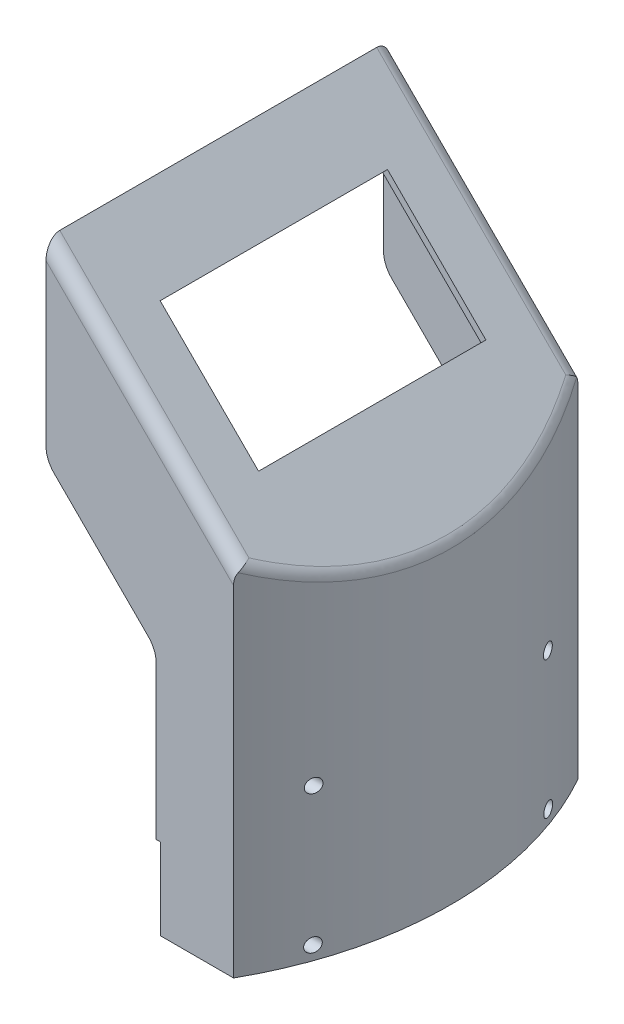
SolidWorks part; units mm, degrees
ref_plane "Front Plane" through (0, 0, 0) normal (0, 0, 1) x (1, 0, 0)
ref_plane "Top Plane" through (0, 0, 0) normal (0, 1, 0) x (1, 0, 0)
ref_plane "Right Plane" through (0, 0, 0) normal (1, 0, 0) x (0, 0, -1)
sketch "Sketch1" plane through (0, 0, 0) normal (0, 1, 0) x (1, 0, 0)
  circle A0 centre (0, 0) radius 254.5
  circle A1 centre (0, 0) radius 234.5
  dimension "D1" = 20
extrude "Boss-Extrude1" add sketch "Sketch1" along normal blind 5
sketch "Sketch2" plane through (0, 5, 0) normal (0, 1, 0) x (1, 0, 0)
  line L0 (254.5, 0) -> (234.5, 0)
  line L1 (221.6873, 125) -> (198.4068, 125)
  line L3 (168.5, 125) -> (165.5, 125) construction
  arc A0 (254.5, 0) -> (221.6873, 125) centre (0, 0) ccw
  circle A2 centre (0, 0) radius 254.5 construction
  circle A7 centre (0, 0) radius 234.5 construction
  arc A8 (198.4068, 125) -> (234.5, 0) centre (0, 0) cw
  circle M1 centre (0, 0) radius 254.5
  circle M2 centre (0, 0) radius 234.5
  dimension "D1" = 0
  dimension "D2" = 0
extrude "Boss-Extrude2" add sketch "Sketch2" along normal blind 500 contours L1 M1 M2 region at (232.9072, 5, -64.0481)
mirror "Mirror1" about plane through (0, 505, 0) normal (0, 0, 1) of "Boss-Extrude2"
sketch "Sketch3" plane through (0, 5, 0) normal (0, 1, 0) x (1, 0, 0)
  line L1 (-254.5, 0) -> (-226.6942, 0)
  line L2 (-254.5, 0) -> (-254.5, 60)
  line L3 (-254.5, 60) -> (-226.6942, 60)
  line L4 (-226.6942, 0) -> (-226.6942, 60)
  arc A0 (221.6873, 125) -> (221.6873, -125) centre (0, 0) ccw construction
  arc A1 (198.4068, 125) -> (198.4068, -125) centre (0, 0) ccw construction
  dimension "D1" = 60
extrude "Cut-Extrude1" cut sketch "Sketch3" against normal blind 500
mirror "Mirror2" about plane through (0, 0, 0) normal (0, 0, 1) of "Cut-Extrude1"
sketch "Sketch4" plane through (0, 505, 0) normal (0, 1, 0) x (1, 0, 0)
  circle A0 centre (0, 0) radius 250.5
  arc A1 (221.6873, -125) -> (221.6873, 125) centre (0, 0) ccw construction
  dimension "D1" = 4
extrude "Cut-Extrude2" cut sketch "Sketch4" against normal blind 500
sketch "Sketch8" plane through (0, 5, 0) normal (0, 1, 0) x (1, 0, 0)
  line L0 (217.0835, 125) -> (165.5835, 125)
  line L1 (165.5835, 125) -> (165.5835, 120)
  line L2 (165.5835, 120) -> (220.0458, 120)
  line L3 (220.0458, 120) -> (220.0458, 125)
  line L4 (221.6873, 125) -> (217.0835, 125) construction
  line L5 (220.0458, 125) -> (217.0835, 125)
  dimension "D1" = 5
  dimension "D2" = 51.5
  dimension "D3" = 220.0458
extrude "Boss-Extrude3" add sketch "Sketch8" along normal blind 500
mirror "Mirror3" about plane through (0, 0, 0) normal (0, 0, 1) of "Boss-Extrude3"
sketch "Sketch10" plane through (0, 0, 0) normal (0, -1, 0) x (1, 0, 0)
  line L0 (165.5835, 125) -> (165.5835, -125)
  line L1 (165.5835, 125) -> (208.5835, 125)
  line L2 (165.5835, -125) -> (208.5835, -125)
  arc A3 (208.5835, 125) -> (208.5835, -125) centre (0, 0) cw
  arc M3 (-226.6942, 60) -> (-226.6942, -60) centre (0, 0) cw
extrude "Boss-Extrude4" add sketch "Sketch10" against normal blind 5 contours L0 L2 L1 M3 region at (195.2098, 0, 0)
sketch "Sketch11" plane through (0, 5, 0) normal (0, 1, 0) x (1, 0, 0)
  line L0 (165.5835, -120) -> (165.5835, 120) construction
  line L1 (165.5835, 93.5) -> (190, 93.5)
  line L2 (165.5835, 93.5) -> (165.5835, -96.5)
  line L3 (165.5835, -96.5) -> (190, -96.5)
  line L4 (190, 93.5) -> (190, -96.5)
  line L5 (188.5, -95) -> (188.5, -75) construction
  line L6 (168.5, -95) -> (188.5, -95) construction
  line L7 (188.5, 95) -> (168.5, 95) construction
  point P10 (178.5, -95)
  dimension "D1" = 1.5
  dimension "D2" = 1.5
  dimension "D3" = 1.5
extrude "Cut-Extrude3" cut sketch "Sketch11" against normal blind 10
sketch "Sketch12" plane through (0, 5, 0) normal (0, 1, 0) x (1, 0, 0)
  line L0 (-276.0044, 0) -> (276.0044, 0) construction
  line L1 (165.5835, 120) -> (185, 120)
  line L2 (165.5835, 120) -> (165.5835, 93.5)
  line L3 (165.5835, 93.5) -> (190, 93.5)
  line L4 (190, 115) -> (190, 93.5)
  line L5 (190, 93.5) -> (213, 93.5)
  line L6 (190, 93.5) -> (190, 75)
  line L7 (190, 75) -> (213, 75)
  line L8 (218, 88.5) -> (218, 80)
  line L9 (218, -88.5) -> (218, -80)
  line L10 (190, -75) -> (213, -75)
  line L11 (190, -93.5) -> (190, -75)
  line L12 (190, -93.5) -> (213, -93.5)
  line L13 (190, -115) -> (190, -93.5)
  line L14 (165.5835, -93.5) -> (190, -93.5)
  line L15 (165.5835, -120) -> (165.5835, -93.5)
  line L16 (165.5835, -120) -> (185, -120)
  arc A0 (213, -93.5) -> (218, -88.5) centre (213, -88.5) ccw
  arc A1 (218, -80) -> (213, -75) centre (213, -80) ccw
  arc A2 (190, -115) -> (185, -120) centre (185, -115) cw
  arc A3 (213, 75) -> (218, 80) centre (213, 80) ccw
  arc A4 (218, 88.5) -> (213, 93.5) centre (213, 88.5) ccw
  arc A5 (190, 115) -> (185, 120) centre (185, 115) ccw
  point P20 (218, -93.5)
  point P23 (218, -75)
  point P26 (190, -120)
  point P29 (218, 75)
  point P32 (218, 93.5)
  point P35 (190, 120)
  line M3 (190, 93.5) -> (190, -96.5)
  line M4 (190, -96.5) -> (165.5835, -96.5)
  line M5 (165.5835, -96.5) -> (165.5835, -120)
  line M6 (165.5835, -120) -> (219.8869, -120)
  dimension "D2" = 5
  dimension "D1" = 28
extrude "Cut-Extrude4" cut sketch "Sketch12" against normal blind 10 contours L8 L5 L7 M3 | L9 A1 L10 L12 A0 M3 | A2 L13 M4 M5 M6 | L4 A5 L1 L2 L3 region at (203.7275, 5, 84.25) region at (203.7275, 5, -84.25) region at (177.6871, 5, 108.1496)
fillet "Fillet1" radius 5 4 edges at (190, 2.5, 93.5) (190, 2.5, -93.5) (190, 2.5, -75) (190, 2.5, 75)
sketch "Sketch15" plane through (0, 5, 0) normal (0, 1, 0) x (1, 0, 0)
  circle A0 centre (242.5, 0) radius 2.5
  circle A1 centre (196.1866, -142.5379) radius 2.5
  circle A2 centre (74.9366, -230.6312) radius 2.5
  circle A3 centre (-74.9366, -230.6312) radius 2.5
  circle A4 centre (-196.1866, -142.5379) radius 2.5
  circle A5 centre (-242.5, 0) radius 2.5
  circle A6 centre (-196.1866, 142.5379) radius 2.5
  circle A7 centre (-74.9366, 230.6312) radius 2.5
  circle A8 centre (74.9366, 230.6312) radius 2.5
  circle A9 centre (196.1866, 142.5379) radius 2.5
  point P23 (0, 0)
  dimension "D1" = 242.5
  dimension "D2" = 10
extrude "Cut-Extrude5" cut sketch "Sketch15" against normal blind 10
sketch "Sketch16" plane through (0, 5, 0) normal (0, 1, 0) x (1, 0, 0)
  line L0 (-226.6942, 60) -> (-247.3262, 60) construction
  line L1 (221.6873, 125) -> (198.4068, 125) construction
  line L2 (-247.3262, 60) -> (-244.2381, 60)
  line L3 (221.6873, 125) -> (218.2367, 125)
  line L4 (-276.0044, 0) -> (276.0044, 0) construction
  line L5 (221.6873, -125) -> (218.2367, -125)
  line L6 (-247.3262, -60) -> (-244.2381, -60)
  arc A0 (221.6873, 125) -> (-247.3262, 60) centre (0, 0) ccw
  arc A1 (218.2367, 125) -> (-244.2381, 60) centre (0, 0) ccw
  arc A2 (218.2367, -125) -> (-244.2381, -60) centre (0, 0) cw
  arc A3 (221.6873, -125) -> (-247.3262, -60) centre (0, 0) cw
  dimension "D1" = 3
extrude "Boss-Extrude5" add sketch "Sketch16" along normal blind 3
sketch "Sketch18" plane through (0, 5, 0) normal (0, 1, 0) x (1, 0, 0)
  circle A0 centre (0, -242.5) radius 2.5
  circle A1 centre (-142.5379, -196.1866) radius 2.5
  circle A2 centre (-230.6312, -74.9366) radius 2.5
  circle A3 centre (-230.6312, 74.9366) radius 2.5
  circle A4 centre (-142.5379, 196.1866) radius 2.5
  circle A5 centre (0, 242.5) radius 2.5
  circle A6 centre (142.5379, 196.1866) radius 2.5
  circle A7 centre (230.6312, 74.9366) radius 2.5
  circle A8 centre (230.6312, -74.9366) radius 2.5
  circle A9 centre (142.5379, -196.1866) radius 2.5
  point P23 (0, 0)
  dimension "D1" = 242.5
  dimension "D2" = 10
extrude "Cut-Extrude6" cut sketch "Sketch18" against normal blind 5
sketch "Sketch19" plane through (0, 0, 0) normal (0, -1, 0) x (1, 0, 0)
  line L1 (193, 20) -> (207, 20)
  line L2 (190, 17) -> (190, -17)
  line L3 (193, -20) -> (207, -20)
  line L4 (210, 17) -> (210, -17)
  line L5 (193, -20) -> (190, -20)
  line L7 (190, -20) -> (190, -17)
  line L8 (193, 20) -> (190, 20)
  line L9 (190, 20) -> (190, 17)
  arc A1 (207, -20) -> (210, -17) centre (207, -17) ccw
  arc A2 (210, 17) -> (207, 20) centre (207, 17) ccw
  point P14 (190, 20)
extrude "Cut-Extrude7" cut sketch "Sketch19" against normal blind 7
fillet "Fillet2" radius 5 2 edges at (190, 2.5, 20) (190, 2.5, -20)
sketch "Sketch21" plane through (0, 5, 0) normal (0, 1, 0) x (1, 0, 0)
  line L0 (207, 20) -> (195, 20) construction
  line L1 (195, -20) -> (207, -20) construction
  line L2 (190, 25) -> (190, 70) construction
  line L3 (190, -70) -> (190, -25) construction
  circle A0 centre (200, 50) radius 2.5
  circle A1 centre (200, -50) radius 2.5
  dimension "D1" = 30
  dimension "D2" = 30
  dimension "D3" = 10
  dimension "D4" = 10
extrude "Cut-Extrude8" cut sketch "Sketch21" against normal blind 10
sketch "Sketch24" plane through (0, 0, 0) normal (0, 0, 1) x (1, 0, 0)
  line L0 (254.5, 0) -> (254.5, 505) construction
  line L1 (268.5989, 234) -> (240.4011, 234)
  line L2 (268.5989, 234) -> (268.5989, 259)
  line L3 (268.5989, 259) -> (240.4011, 259)
  line L4 (240.4011, 234) -> (240.4011, 259)
  line L5 (268.5989, 234) -> (240.4011, 259) construction
  line L6 (268.5989, 259) -> (240.4011, 234) construction
  line L7 (221.6873, 8) -> (-247.3262, 8) construction
  point P0 (254.5, 246.5)
  dimension "D1" = 226
  dimension "D2" = 25
extrude "Cut-Extrude11" cut sketch "Sketch24" against normal mid plane 90
fillet "Fillet3" radius 2 4 edges at (248.4575, 259, 45) (248.4575, 234, 45) (248.4575, 234, -45) (248.4575, 259, -45)
sketch "Sketch25" plane through (0, 0, 0) normal (0, -1, 0) x (1, 0, 0)
  circle A0 centre (0, 0) radius 315.9931
extrude "Cut-Extrude12" cut sketch "Sketch25" against normal blind 277
sketch "Sketch26" plane through (0, 277, 0) normal (0, -1, 0) x (1, 0, 0)
  line L0 (188.5835, -120) -> (188.5835, -60)
  line L1 (165.5835, -120) -> (219.8869, -120) construction
  line L2 (165.5835, 120) -> (219.8869, 120) construction
  line L4 (188.5835, -120) -> (219.8869, -120)
  line L5 (188.5835, 120) -> (219.8869, 120)
  line L6 (188.5835, -60) -> (243.2082, -60)
  line L7 (188.5835, 120) -> (188.5835, 60)
  line L8 (188.5835, 60) -> (243.2082, 60)
  arc A0 (219.8869, -120) -> (250.5, 0) centre (0, 0) cw
  arc A1 (219.8869, -120) -> (219.8869, 120) centre (0, 0) ccw construction
  line M9 (165.5835, 120) -> (219.8869, 120)
  arc M10 (219.8869, 120) -> (219.8869, -120) centre (0, 0) cw
  line M11 (219.8869, -120) -> (165.5835, -120)
  dimension "D1" = 60
  dimension "D2" = 54.6247
extrude "Boss-Extrude6" add sketch "Sketch26" against normal blind 150 contours L6 L0 M11 M10 | L7 L8 M10 M9 region at (211.3196, 277, -87.3868) region at (211.3196, 277, 87.3868)
sketch "Sketch30" plane through (0, 505, 0) normal (0, 1, 0) x (1, 0, 0)
  line L12 (219.8869, 120) -> (217.6057, 120)
  line L13 (219.8869, 120) -> (188.5835, 120) construction
  line L14 (219.8869, -120) -> (217.6057, -120)
  line L15 (188.5835, -120) -> (219.8869, -120) construction
  arc A4 (218.1313, -119.0419) -> (218.1313, 119.0419) centre (0, 0) ccw
  arc A5 (218.1313, -119.0419) -> (218.1313, 119.0419) centre (0, 0) ccw
  circle A6 centre (0, 0) radius 248.5
  arc A7 (219.8869, -120) -> (219.8869, 120) centre (0, 0) ccw
  arc A8 (219.8869, -120) -> (219.8869, 120) centre (0, 0) ccw
  line M8 (165.5835, 120) -> (219.8869, 120)
  arc M9 (219.8869, 120) -> (219.8869, -120) centre (0, 0) cw
  line M10 (219.8869, -120) -> (165.5835, -120)
  dimension "D1" = 2
  dimension "D2" = 0
extrude "Boss-Extrude8" add sketch "Sketch30" against normal blind 228 contours A6 A5 M10 M9 M8 region at (250.2578, 505, 0)
sketch "Sketch33" plane through (0, 0, 0) normal (0, 0, 1) x (1, 0, 0)
  line L0 (254.5, 505) -> (85.5835, 673.9165)
  line L2 (165.5835, 505) -> (254.5, 505)
  line L3 (165.5835, 505) -> (85.5835, 505)
  line L6 (85.5835, 505) -> (85.5835, 673.9165)
  point P3 (88.5835, 670.7629)
  point P7 (88.5835, 672.6248)
  dimension "D1" = 45
  dimension "D2" = 80
extrude "Boss-Extrude9" add sketch "Sketch33" along normal mid plane 250
sketch "Sketch34" plane through (0, 505, 0) normal (0, -1, 0) x (-1, 0, 0)
  line L0 (-221.6873, -125) -> (-254.5, -125)
  line L1 (-254.5, -125) -> (-254.5, 0) construction
  line L2 (-254.5, -125) -> (-254.5, 126.7594)
  line L3 (-221.6873, 125) -> (-254.5, 125)
  arc A0 (-221.6873, -125) -> (-254.5, 0) centre (0, 0) ccw
  arc A1 (-221.6873, 125) -> (-221.6873, -125) centre (0, 0) ccw construction
  line M1 (-254.5, -125) -> (-221.6873, -125)
  arc M2 (-221.6873, -125) -> (-254.5, 0) centre (0, 0) cw
  line M3 (-254.5, 0) -> (-254.5, -125)
extrude "Cut-Extrude15" cut sketch "Sketch34" against normal blind 250 contours M3 M1 M2 | A0 L3 L2 region at (244.7754, 505, 94.1672) region at (244.7754, 505, -94.1672)
sketch "Sketch35" plane through (188.5835, 0, 0) normal (-1, 0, 0) x (0, 0, 1)
  line L0 (-120, 277) -> (-60, 277) construction
  line L1 (-120, 427) -> (-120, 277) construction
  line L2 (0, -48.9041) -> (0, 48.9041) construction
  circle A0 centre (-85, 386.9994) radius 2.5
  circle A1 centre (-85.3604, 287) radius 2.5
  circle A2 centre (85.3604, 287) radius 2.5
  circle A3 centre (85, 386.9994) radius 2.5
  dimension "D1" = 100
  dimension "D2" = 10
  dimension "D3" = 35
extrude "Cut-Extrude16" cut sketch "Sketch35" against normal blind 10
sketch "Sketch37" plane through (0, 0, 0) normal (0, 0, 1) x (1, 0, 0)
  line L0 (85.5835, 666.8454) -> (85.5835, 505)
  line L1 (85.5835, 505) -> (165.5835, 505) construction
  line L2 (85.5835, 505) -> (217.6057, 505)
  line L3 (217.6057, 534.8232) -> (85.5835, 666.8454)
  line L7 (221.6873, 537.8127) -> (85.5835, 673.9165) construction
  line L8 (217.6057, 427) -> (217.6057, 505) construction
  line L10 (217.6057, 505) -> (217.6057, 534.8232)
  line L11 (85.5835, 673.9165) -> (85.5835, 505) construction
  point P5 (217.6057, 534.8654)
  point P13 (217.4488, 534.9801)
  dimension "D1" = 0
  dimension "D2" = 5
extrude "Cut-Extrude18" cut sketch "Sketch37" against normal mid plane 240 contours L2 L3 L0 region at (136.4384, 560.4953, 0)
sketch "Sketch40" plane through (0, 0, -125) normal (0, 0, -1) x (-1, 0, 0)
  line L0 (-165.5835, 505) -> (-85.5835, 585)
  line L2 (-85.5835, 585) -> (-85.5835, 505)
  line L3 (-85.5835, 505) -> (-165.5835, 505)
  line L4 (-85.5835, 673.9165) -> (-85.5835, 505) construction
  line L5 (-221.6873, 537.8127) -> (-85.5835, 673.9165) construction
  dimension "D1" = 0
  dimension "D2" = 0
extrude "Cut-Extrude19" cut sketch "Sketch40" against normal blind 369
sketch "Sketch41" plane through (0, 505, 0) normal (0, -1, 0) x (1, 0, 0)
  line L0 (217.6057, 120) -> (217.6057, -120)
  circle A0 centre (0, 0) radius 248.5
  arc M1 (217.6057, -120) -> (217.6057, 120) centre (0, 0) ccw
  line M2 (217.6057, 120) -> (217.6057, -120)
extrude "Boss-Extrude10" add sketch "Sketch41" along normal blind 228 contours M2 M1 region at (230.0317, 505, 0)
sketch "Sketch36" plane through (198.5835, 0, 0) normal (-1, 0, 0) x (0, 0, 1)
  line L0 (0, -48.9041) -> (0, 48.9041) construction
  circle A0 centre (-85, 386.9994) radius 5
  circle A1 centre (-85.3604, 287) radius 5
  circle A2 centre (85.3604, 287) radius 5
  circle A3 centre (85, 386.9994) radius 5
extrude "Cut-Extrude17" cut sketch "Sketch36" against normal blind 110
fillet "Fillet5" radius 10 1 edges at (217.6057, 534.8232, 0)
fillet "Fillet7" radius 10 3 edges at (153.6354, 605.8646, 125) (254.5, 505, 0) (153.6354, 605.8646, -125)
sketch "Sketch43" plane through (376.2145, 376.2145, 0) normal (-0.7071, -0.7071, 0) x (0, 0, 1)
  line L0 (-120, 228.4488) -> (120, 228.4488) construction
  line L1 (82.5, 257.9488) -> (-82.5, 257.9488)
  line L2 (82.5, 257.9488) -> (82.5, 358.9488)
  line L3 (82.5, 358.9488) -> (-82.5, 358.9488)
  line L4 (-82.5, 257.9488) -> (-82.5, 358.9488)
  line L5 (82.5, 257.9488) -> (-82.5, 358.9488) construction
  line L6 (82.5, 358.9488) -> (-82.5, 257.9488) construction
  point P0 (0, 308.4488)
  point P7 (0, 228.4488)
  dimension "D1" = 165
  dimension "D2" = 0
  dimension "D3" = 101
  dimension "D4" = 80
extrude "Cut-Extrude20" cut sketch "Sketch43" against normal blind 10
fillet "Fillet8" radius 10 6 edges at (217.6057, 478.8405, 120) (216.8445, 534.5079, 120) (217.6057, 478.8405, -120) (216.8445, 534.5079, -120) (150.1301, 602.2988, 120) (150.1301, 602.2988, -120)
sketch "Sketch44" plane through (0, 0, -125) normal (0, 0, -1) x (-1, 0, 0)
  line L0 (-85.5835, 585) -> (-165.5835, 505)
  line L1 (-165.5835, 505) -> (-165.5835, 455)
  line L2 (-165.5835, 505) -> (-165.5835, 277) construction
  line L3 (-165.5835, 455) -> (-85.5835, 535)
  line L4 (-85.5835, 535) -> (-85.5835, 585)
  point P4 (0, 0)
  dimension "D1" = 50
  dimension "D2" = 50
extrude "Boss-Extrude12" add sketch "Sketch44" against normal blind 5
mirror "Mirror6" about plane through (0, 0, 0) normal (0, 0, 1) of "Boss-Extrude12"
fillet "Fillet9" radius 20 4 edges at (165.5835, 455, 122.5) (85.5835, 535, 122.5) (165.5835, 455, -122.5) (85.5835, 535, -122.5)
sketch "Sketch46" plane through (0, 0, -125) normal (0, 0, -1) x (-1, 0, 0)
  line L0 (-168.5, 336) -> (-165.5, 336) construction
  line L1 (-165.5835, 277) -> (-168.5835, 277)
  line L2 (-165.5835, 277) -> (-165.5835, 336)
  line L3 (-165.5835, 336) -> (-168.5835, 336)
  line L4 (-168.5835, 277) -> (-168.5835, 336)
  dimension "D1" = 3
  dimension "D2" = 0
extrude "Cut-Extrude21" cut sketch "Sketch46" against normal blind 5
mirror "Mirror7" about plane through (0, 0, 0) normal (0, 0, 1) of "Cut-Extrude21"
